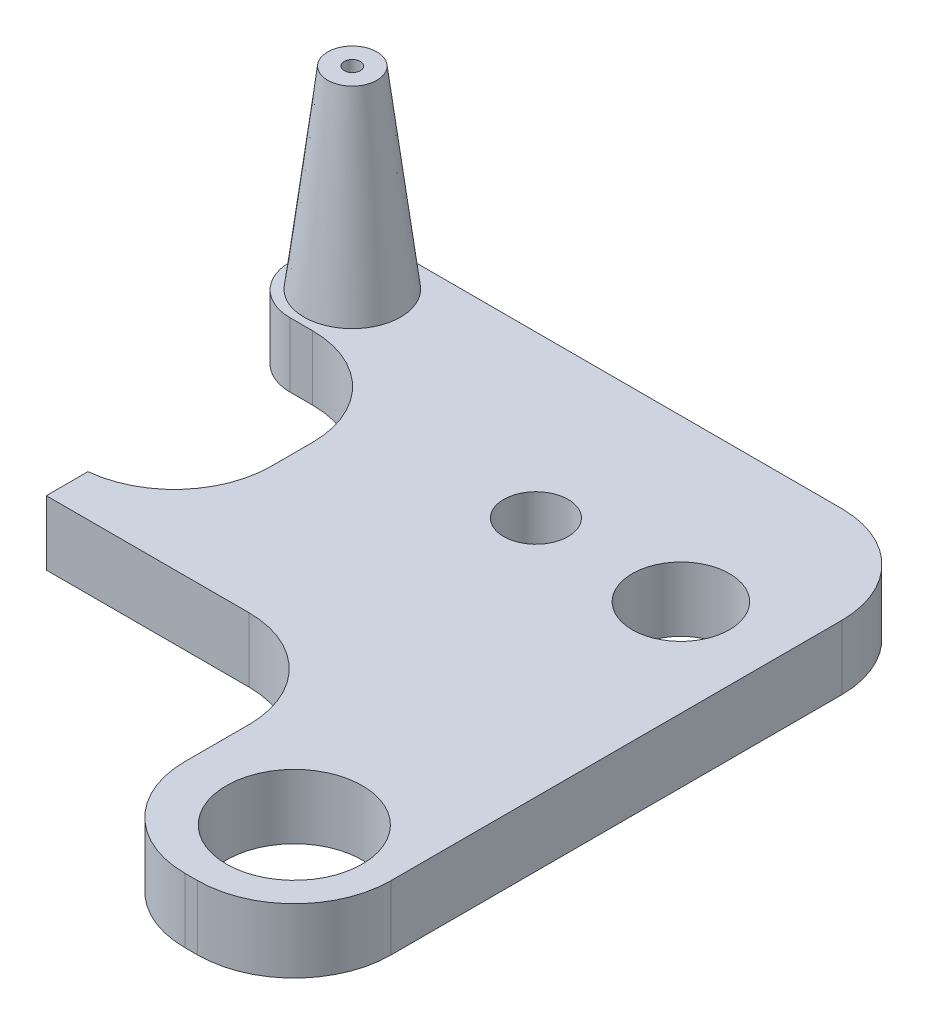
SolidWorks part; units mm, degrees
ref_plane "Front Plane" through (0, 0, 0) normal (0, 0, 1) x (1, 0, 0)
ref_plane "Top Plane" through (0, 0, 0) normal (0, 1, 0) x (1, 0, 0)
ref_plane "Right Plane" through (0, 0, 0) normal (1, 0, 0) x (0, 0, -1)
sketch "Sketch1" plane through (0, 0, 0) normal (0, 1, 0) x (1, 0, 0)
  line L0 (23.9959, -35) -> (56.9959, -35)
  line L4 (88.9959, -25) -> (88.9959, 25)
  line L5 (0, -39.6238) -> (0, 46.4731) construction
  line L6 (23.9959, 0) -> (23.9959, -28.538)
  line L7 (56.9959, -75) -> (88.9959, -75)
  line L8 (88.9959, -75) -> (88.9959, -25)
  line L10 (17.5, 25) -> (88.9959, 25)
  line L11 (73.9959, 41.1849) -> (73.9959, -116.2589) construction
  line L12 (23.9959, -28.538) -> (10.4959, -28.538)
  line L13 (10.4959, -28.538) -> (10.4959, -35)
  line L14 (10.4959, -35) -> (23.9959, -35)
  line L16 (17.5, 25) -> (-2.0041, 25)
  line L17 (-2.0041, 25) -> (-2.0041, 7.8405)
  line L19 (23.9959, 0) -> (23.9959, 7.8405)
  line L20 (23.9959, 7.8405) -> (-2.0041, 7.8405)
  line L21 (23.9959, 0) -> (73.9959, 0) construction
  line L22 (56.9959, -35) -> (56.9959, -75)
  circle A6 centre (73.9959, 0) radius 7.55
  circle A7 centre (51.4959, 0) radius 5
  circle A9 centre (73.9959, -60) radius 10.55
  circle A10 centre (5.147, 17.7557) radius 2.5 construction
  point P0 (0, 0)
  dimension "D3" = 22.5
  dimension "D5" = 100
  dimension "D7" = 15.1
  dimension "D4" = 10
  dimension "D1" = 60
  dimension "D8" = 21.1
  dimension "D13" = 5
  dimension "D2" = 13.5
  dimension "D6" = 91
  dimension "D9" = 15
  dimension "D10" = 50
  dimension "D11" = 32
extrude "Boss-Extrude1" add sketch "Sketch1" along normal blind 10
sketch "Sketch2" plane through (10.4959, 0, 0) normal (-1, 0, 0) x (0, 0, 1)
  line L0 (31.769, 0) -> (31.769, 10) construction
  line L1 (28.538, 0) -> (35, 0) construction
  line L2 (28.538, 5) -> (35, 5) construction
  line L3 (28.538, 10) -> (28.538, 0) construction
  line L5 (28.538, 10) -> (35, 10) construction
  circle A0 centre (31.769, 5) radius 1.25
  point P10 (31.769, 5)
  dimension "D1" = 2.5
extrude "Cut-Extrude1" cut sketch "Sketch2" against normal blind 10 contours A0
sketch "Sketch4" plane through (0, 10, 0) normal (0, 1, 0) x (1, 0, 0)
  line L2 (88.9959, 25) -> (-2.0041, 25) construction
  line L3 (-2.0041, 25) -> (-2.0041, 7.8405) construction
  circle A0 centre (6.4959, 16.5) radius 7.5
  dimension "D1" = 15
  dimension "D2" = 8.5
  dimension "D3" = 8.5
extrude "Boss-Extrude2" add sketch "Sketch4" along normal blind 30 draft 7 contours A0
sketch "Sketch5" plane through (0, 40, 0) normal (0, 1, 0) x (1, 0, 0)
  line L0 (-2.0041, 25) -> (-2.0041, 7.8405) construction
  line L1 (88.9959, 25) -> (-2.0041, 25) construction
  circle A0 centre (6.4959, 16.5) radius 1.25
  dimension "D1" = 8.5
  dimension "D2" = 8.5
  dimension "D3" = 2.5
extrude "Cut-Extrude2" cut sketch "Sketch5" against normal blind 10
fillet "Fillet1" radius 15 6 edges at (56.9959, 5, 35) (23.9959, 5, 28.538) (23.9959, 5, -7.8405) (88.9959, 5, -25) (88.9959, 5, 75) (56.9959, 5, 75)
fillet "Fillet2" radius 7.5 2 edges at (-2.0041, 5, -7.8405) (-2.0041, 5, -25)
